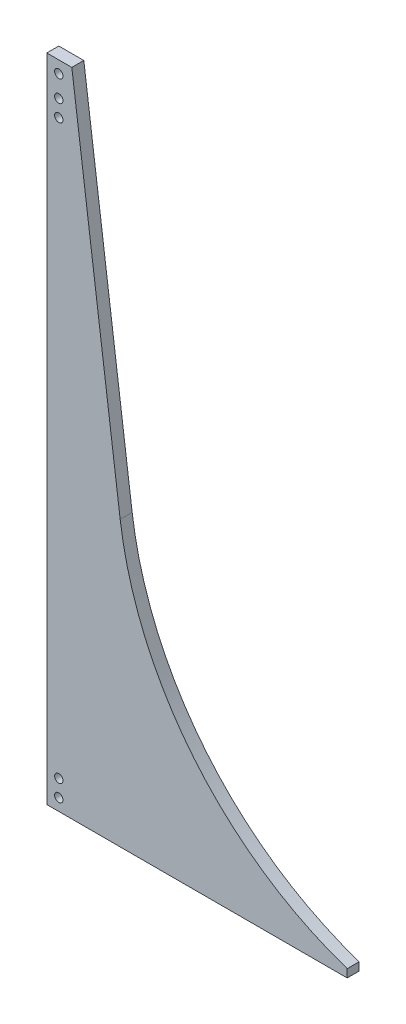
SolidWorks part; units mm, degrees
material "Maple"
ref_plane "Front Plane" through (0, 0, 0) normal (0, 0, 1) x (1, 0, 0)
ref_plane "Top Plane" through (0, 0, 0) normal (0, 1, 0) x (1, 0, 0)
ref_plane "Right Plane" through (0, 0, 0) normal (1, 0, 0) x (0, 0, -1)
sketch "Sketch1" plane through (0, 0, 0) normal (0, 0, 1) x (1, 0, 0)
  line L1 (0, 0) -> (0, 990.6)
  line L2 (0, 990.6) -> (38.1, 990.6)
  line L11 (38.1, 990.6) -> (111.6674, 431.8)
  line L13 (0, 0) -> (457.2, 0)
  line L14 (457.2, 0) -> (457.2, 12.3171)
  arc A1 (111.6674, 431.8) -> (457.2, 12.3171) centre (620.3686, 498.7718) ccw
  dimension "D1" = 513.0908
  dimension "D2" = 12.3171
  dimension "D3" = 457.2
  dimension "D4" = 38.1
  dimension "D5" = 97.5
  dimension "D6" = 558.8
extrude "Boss-Extrude1" add sketch "Sketch1" along normal mid plane 18.2562
sketch "Sketch2" plane through (0, 0, 9.1281) normal (0, 0, 1) x (1, 0, 0)
  line L0 (0, 990.6) -> (0, 0) construction
  line L1 (38.1, 990.6) -> (0, 990.6) construction
  line L5 (0, 0) -> (457.2, 0) construction
  line L6 (0, 990.6) -> (0, 0) construction
  line L7 (38.1, 990.6) -> (0, 990.6) construction
  circle A0 centre (18.2562, 972.3438) radius 6.35
  circle A1 centre (18.2562, 18.2562) radius 6.35
  circle A4 centre (18.2562, 43.6562) radius 6.35
  circle A5 centre (18.2562, 939.8) radius 6.35
  circle A6 centre (18.2562, 914.4) radius 6.35
  dimension "D2" = 12.7
  dimension "D4" = 12.7
  dimension "D10" = 12.7
  dimension "D13" = 12.7
  dimension "D14" = 12.7
  dimension "D15" = 25.4
  dimension "D16" = 18.2562
  dimension "D17" = 50.8
  dimension "D18" = 18.2562
  dimension "D6" = 18.2562
  dimension "D1" = 18.2562
  dimension "D3" = 18.2562
  dimension "D5" = 18.2562
  dimension "D11" = 25.4
  dimension "D12" = 18.2562
extrude "Cut-Extrude1" cut sketch "Sketch2" against normal through all
